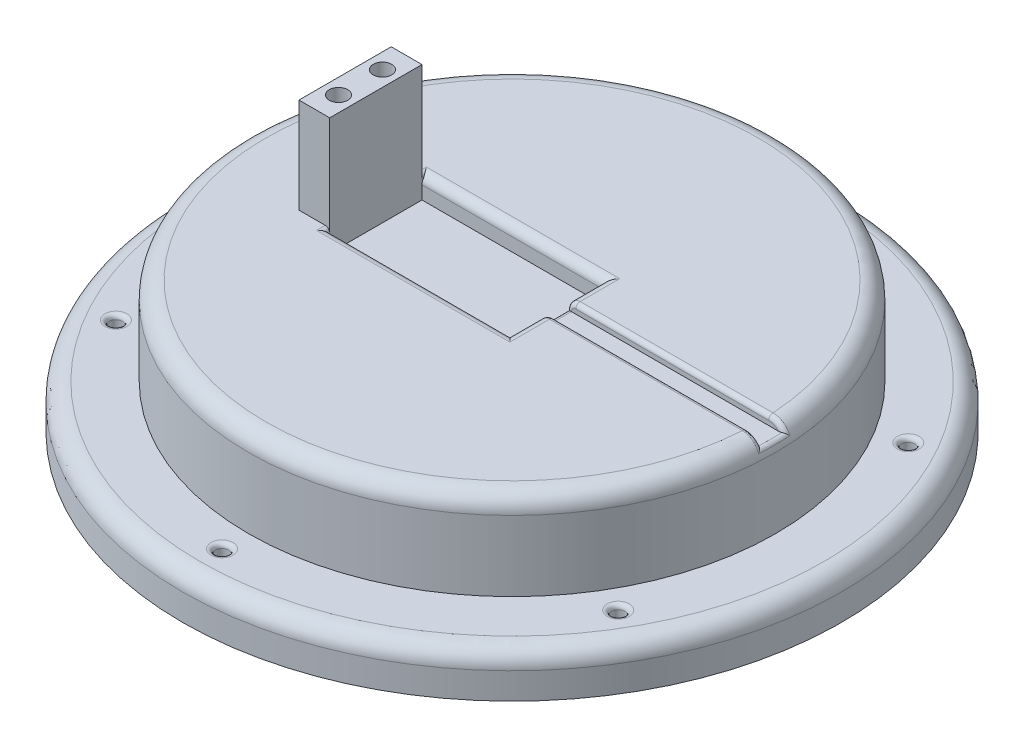
SolidWorks part; units mm, degrees
ref_plane "Plan de face" through (0, 0, 0) normal (0, 0, 1) x (1, 0, 0)
ref_plane "Plan de dessus" through (0, 0, 0) normal (0, 1, 0) x (1, 0, 0)
ref_plane "Plan de droite" through (0, 0, 0) normal (1, 0, 0) x (0, 0, -1)
sketch "Esquisse1" plane through (0, 0, 0) normal (0, 1, 0) x (1, 0, 0)
  line L0 (0, 0) -> (0, 47.0919) construction
  line L1 (0, 0) -> (92.6466, 0) construction
  circle A0 centre (0, 0) radius 75
  dimension "D1" = 150
extrude "Boss.-Extru.1" add sketch "Esquisse1" along normal blind 10
sketch "Esquisse2" plane through (0, 10, 0) normal (0, 1, 0) x (1, 0, 0)
  line L0 (0, 0) -> (0, 98.5046) construction
  line L1 (0, 0) -> (154.8183, 0) construction
  circle A0 centre (0, 0) radius 60
  dimension "D1" = 120
extrude "Boss.-Extru.2" add sketch "Esquisse2" along normal blind 20
sketch "Esquisse3" plane through (0, 10, 0) normal (0, 1, 0) x (1, 0, 0)
  circle A0 centre (0, 66) radius 1.5
  circle A1 centre (57.1577, 33) radius 1.5
  circle A2 centre (57.1577, -33) radius 1.5
  circle A3 centre (0, -66) radius 1.5
  circle A4 centre (-57.1577, -33) radius 1.5
  circle A5 centre (-57.1577, 33) radius 1.5
  point P15 (0, 0)
  dimension "D1" = 3
  dimension "D2" = 66
  dimension "D3" = 6
extrude "Enlèv. mat.-Extru.1" cut sketch "Esquisse3" against normal through all
fillet "Congé1" radius 1 6 edges at (-57.1577, 10, 34.5) (0, 10, 67.5) (57.1577, 10, 34.5) (57.1577, 10, -31.5) (0, 10, -64.5) (-57.1577, 10, -31.5)
fillet "Congé2" radius 4 2 edges at (0, 10, 75) (0, 30, 60)
sketch "Esquisse4" plane through (0, 30, 0) normal (0, 1, 0) x (1, 0, 0)
  line L0 (0, 0) -> (0, 123.1569) construction
  line L1 (0, 0) -> (89.3073, 0) construction
  line L3 (-31, 10.5) -> (10, 10.5)
  line L4 (-31, 10.5) -> (-31, -10.5)
  line L5 (-31, -10.5) -> (10, -10.5)
  line L6 (10, 10.5) -> (10, -10.5)
  point P4 (0, 0)
  dimension "D1" = 10
  dimension "D2" = 31
  dimension "D3" = 21
extrude "Enlèv. mat.-Extru.2" cut sketch "Esquisse4" against normal blind 5
fillet "Congé3" radius 2 3 edges at (-10.5, 30, 10.5) (10, 30, 0) (-10.5, 30, -10.5)
sketch "Esquisse6" plane through (10, 0, 0) normal (-1, 0, 0) x (0, 0, 1)
  line L0 (0, 0) -> (0, 84.5069) construction
  line L1 (-12.5, 30) -> (12.5, 30) construction
  line L2 (-12.5, 30) -> (12.5, 30)
  line L3 (56, 30) -> (-56, 30) construction
  line L4 (-2.5, 28) -> (2.5, 28)
  line L5 (-2.5, 28) -> (-2.5, 30)
  line L6 (-2.5, 30) -> (2.5, 30)
  line L7 (2.5, 28) -> (2.5, 30)
  line M7 (10.5, 28) -> (-10.5, 28)
  dimension "D1" = 2
  dimension "D2" = 5
extrude "Enlèv. mat.-Extru.3" cut sketch "Esquisse6" against normal through all contours L0 L7 L6 M7 | L4 L0 L2 L5 region at (10, 29, -1.25) region at (10, 29, 1.25)
fillet "Congé4" radius 1 8 edges at (57.6989, 29.5954, -2.5) (10.5858, 29.4142, -2.5) (57.6989, 29.5954, 2.5) (10.5858, 29.4142, 2.5) (10, 28, 0) (59.4641, 28, 0) (33.9721, 30, -2.5) (33.9721, 30, 2.5)
sketch "Esquisse7" plane through (0, 30, 0) normal (0, 1, 0) x (1, 0, 0)
  line L0 (0, 0) -> (-58.7915, 0) construction
  line L1 (-31, 10.5) -> (-31, -10.5)
  line L2 (-31, -10.5) -> (-38, -10.5)
  line L3 (-38, -10.5) -> (-38, 10.5)
  line L4 (-38, 10.5) -> (-31, 10.5)
  dimension "D1" = 7
extrude "Boss.-Extru.3" add sketch "Esquisse7" along normal blind 21.7
fillet "Congé7" radius 1 2 edges at (-31, 30, 11.5) (-31, 30, -11.5)
sketch "Esquisse8" plane through (0, 25, 0) normal (0, 1, 0) x (1, 0, 0)
  line L0 (10, -10.5) -> (-31, 10.5) construction
  line L1 (10, 10.5) -> (-31, -10.5) construction
  point P8 (-10.5, 0)
hole_wizard "Trou taraudé M51" positions "Esquisse12" profile "Esquisse13" tap size "M5" standard "ISO"
sketch "Esquisse12" plane through (0, 51.7, 0) normal (0, 1, 0) x (1, 0, 0)
  circle A0 centre (-34.5, 5) radius 2.1
  circle A1 centre (-34.5, -5) radius 2.1
  point P0 (-34.5, 5)
  point P3 (-34.5, -5)
  dimension "D1" = 4.2
  dimension "D2" = 4.2
sketch "Esquisse13" plane through (-34.5, 51.7, -5) normal (1, 0, 0) x (0, 0, 1)
  line L0 (0, 0) -> (0, 26.2618)
  line L1 (0, 26.2618) -> (2.1, 25)
  line L2 (2.1, 25) -> (2.1, 0)
  line L5 (2.1, 0) -> (0, 0)
  line L10 (0, 26.2618) -> (-2.1, 25) construction
  line L11 (0, -6.35) -> (0, 107.95) construction
  dimension "Diamètre du trou pour taraudage" = 4.2
  dimension "Profondeur du trou pour taraudage" = 25
  dimension "Angle de pointe" = 118
cosmetic thread "Filetage de perçage1"
cosmetic thread "Filetage de perçage2"
sketch "Esquisse14" plane through (0, 30, 0) normal (0, 1, 0) x (1, 0, 0)
  circle A0 centre (0, 0) radius 50 construction
  circle A1 centre (0, 0) radius 43 construction
  point P4 (-41.4032, 11.6094)
  dimension "D1" = 7
  dimension "D2" = 100
  dimension "D3" = 86
  dimension "D4" = 3.5794
sketch "Esquisse15" plane through (0, 0, 0) normal (0, 0, 1) x (1, 0, 0)
  circle A0 centre (-34.5, 5) radius 2.1
  circle A1 centre (-34.5, -5) radius 2.1
  point P0 (-34.5, 5)
  point P3 (-34.5, -5)
  dimension "D1" = 4.2
  dimension "D2" = 4.2
